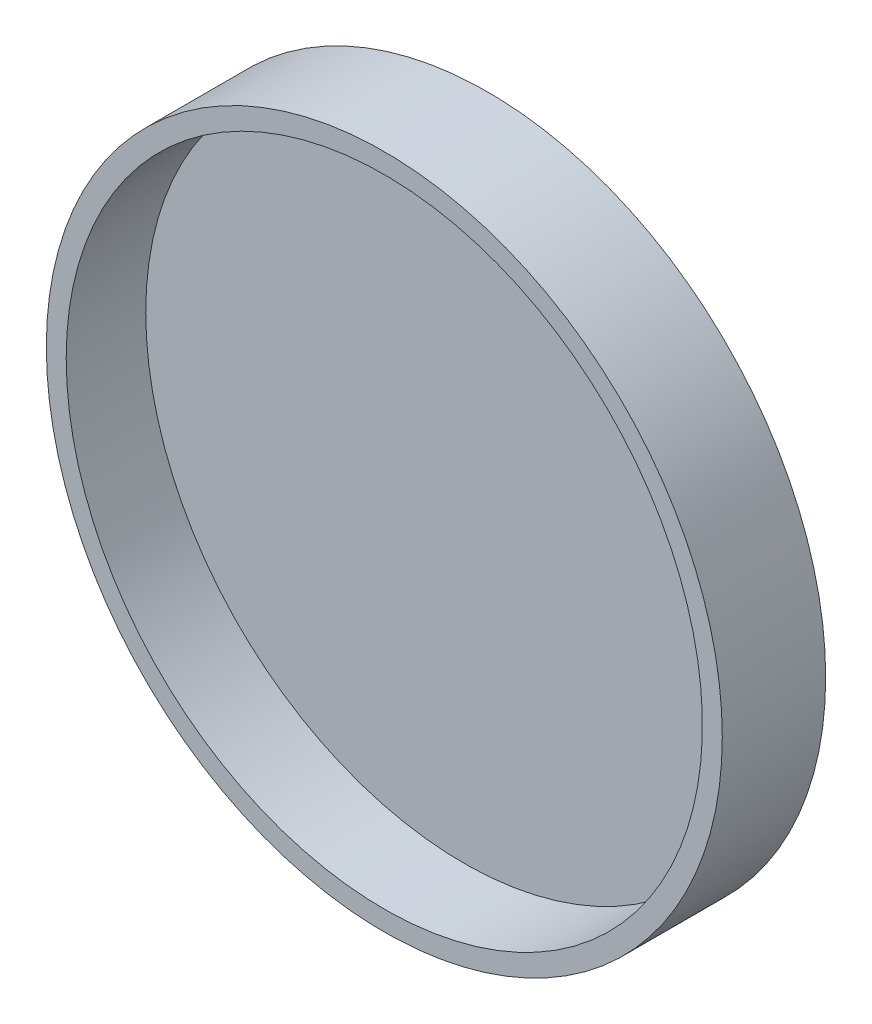
SolidWorks part; units mm, degrees
ref_plane "Front Plane" through (0, 0, 0) normal (0, 0, 1) x (1, 0, 0)
ref_plane "Top Plane" through (0, 0, 0) normal (0, 1, 0) x (1, 0, 0)
ref_plane "Right Plane" through (0, 0, 0) normal (1, 0, 0) x (0, 0, -1)
sketch "Sketch1" plane through (0, 0, 0) normal (0, 0, 1) x (1, 0, 0)
  circle A0 centre (0, 0) radius 53.975
  dimension "D1" = 107.95
extrude "Boss-Extrude1" add sketch "Sketch1" along normal blind 3.81
sketch "Sketch2" plane through (0, 0, 3.81) normal (0, 0, 1) x (1, 0, 0)
  circle A0 centre (0, 0) radius 50.8
  circle A2 centre (0, 0) radius 53.975
  dimension "D1" = 101.6
extrude "Boss-Extrude2" add sketch "Sketch2" along normal blind 12.7
equation "\"D1@Boss-Extrude1\"=0.15"
